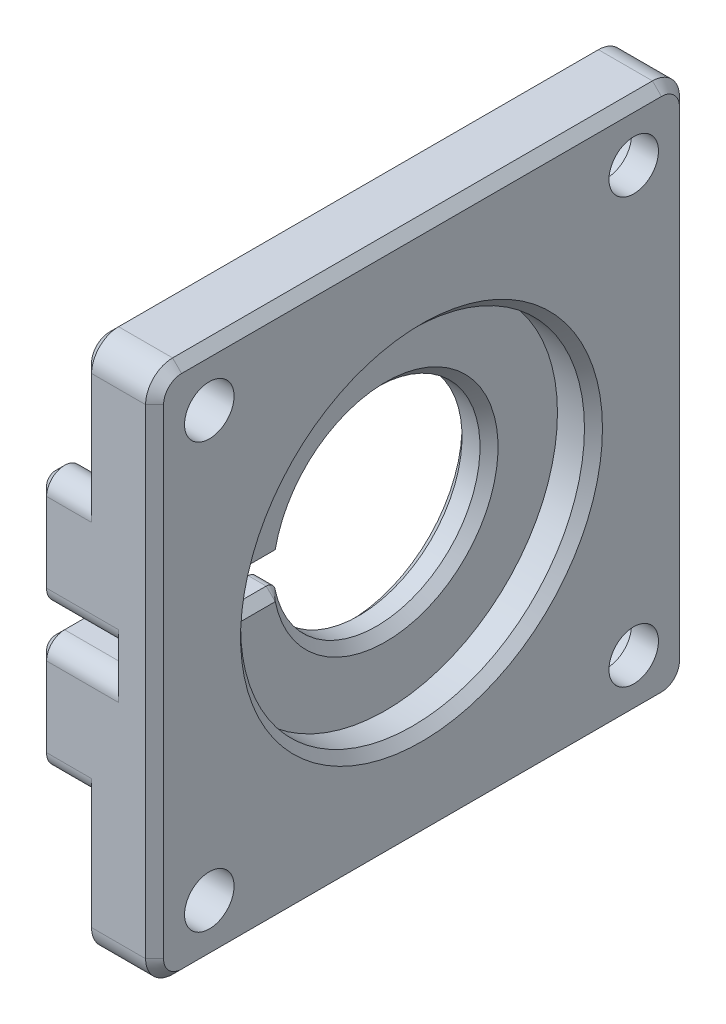
SolidWorks part; units mm, degrees
note: The reader was unsure of these and kept them because the rebuilt part matched: shared geometry of "Sketch1<3>".
ref_plane "Front Plane" through (0, 0, 0) normal (0, 0, 1) x (1, 0, 0)
ref_plane "Top Plane" through (0, 0, 0) normal (0, 1, 0) x (1, 0, 0)
ref_plane "Right Plane" through (0, 0, 0) normal (1, 0, 0) x (0, 0, -1)
sketch "Sketch1" plane through (0, 0, 0) normal (1, 0, 0) x (0, 0, -1)
  line L1 (-23.5714, 23.5714) -> (23.5714, 23.5714) construction
  line L2 (-23.5714, 23.5714) -> (-23.5714, -23.5714) construction
  line L3 (-23.5714, -23.5714) -> (23.5714, -23.5714) construction
  line L4 (23.5714, 23.5714) -> (23.5714, -23.5714) construction
  line L5 (-23.5714, 23.5714) -> (23.5714, -23.5714) construction
  line L6 (-23.5714, -23.5714) -> (23.5714, 23.5714) construction
  line L7 (-29.65, 29.65) -> (29.65, 29.65)
  line L8 (-29.65, 29.65) -> (-29.65, -29.65)
  line L9 (-29.65, -29.65) -> (29.65, -29.65)
  line L10 (29.65, 29.65) -> (29.65, -29.65)
  line L11 (-29.65, 29.65) -> (29.65, -29.65) construction
  line L12 (-29.65, -29.65) -> (29.65, 29.65) construction
  circle A0 centre (0, 0) radius 33.335 construction
  circle A1 centre (0, 0) radius 19.1
  circle A2 centre (0, 0) radius 11.5
  circle A3 centre (-23.5714, 23.5714) radius 2.75
  circle A4 centre (23.5714, 23.5714) radius 2.75
  circle A5 centre (23.5714, -23.5714) radius 2.75
  circle A6 centre (-23.5714, -23.5714) radius 2.75
  point P6 (0, 0)
  point P13 (0, 0)
  dimension "D1" = 66.67
  dimension "D3" = 38.2
  dimension "D4" = 23
  dimension "D5" = 5.5
  dimension "D2" = 59.3
extrude "Boss-Extrude1" add sketch "Sketch1" along normal blind 4 contours L10 L7 L8 L9 A1 | A3 | A4 | A5 | A6
extrude "Boss-Extrude2" add sketch "Sketch1<3>" against normal blind 4 contours L10 L7 L8 L9 A1 | A1 A2 | A4 | A3 | A6 | A5
sketch "Sketch1<3>" plane through (0, 0, 0) normal (1, 0, 0) x (0, 0, -1) same geometry as "Sketch1"
sketch "Sketch18" plane through (-4, 0, 0) normal (-1, 0, 0) x (0, 0, 1)
  line L0 (29.65, 17.15) -> (12.5, 0)
  line L1 (29.65, 29.65) -> (29.65, -29.65) construction
  line L2 (12.5, 0) -> (29.65, -17.15)
  line L3 (29.65, -17.15) -> (29.65, 17.15)
  line L4 (12.5, 0) -> (0, 0) construction
  line L5 (14, 1.5) -> (29.65, 1.5)
  line L6 (29.65, -1.5) -> (14, -1.5)
  line M7 (29.65, -29.65) -> (29.65, 29.65)
  dimension "D1" = 12.5
  dimension "D2" = 45
  dimension "D3" = 3
extrude "Boss-Extrude4" add sketch "Sketch18" along normal blind 5 contours L6 L2 M7 | L0 L5 L3
sketch "Sketch20" plane through (0, 0, 0) normal (0, 0, 1) x (1, 0, 0)
  line L0 (-4, 1.5) -> (-1.5, 1.5)
  line L1 (-1.5, -1.5) -> (-4, -1.5)
  line L2 (-4, -1.5) -> (-4, 1.5)
  line L3 (-1.5, 1.5) -> (0, 1.5)
  line L4 (0, 1.5) -> (0, -1.5)
  line L5 (0, -1.5) -> (-1.5, -1.5)
  arc A0 (-1.5, 1.5) -> (-1.5, -1.5) centre (-1.5, 0) cw
  dimension "D1" = 4
extrude "Cut-Extrude1" cut sketch "Sketch20" along normal through all contours L3 A0 L4 | A0 L0 L2 L1 | L4 A0 L5
sketch "Sketch13" plane through (-4, 0, 0) normal (1, 0, 0) x (0, 0, -1)
  point P0 (-23.5714, 23.5714)
  point P9 (-23.5714, -23.5714)
hole_wizard "M5 Clearance Hole1" positions "Sketch13" profile "Sketch12" hole size "M5" standard "ANSI Metric" end condition through all
sketch "Sketch12" plane through (-4, 23.5714, 23.5714) normal (0, 1, 0) x (0, 0, 1)
  line L0 (0, 0) -> (0, 8)
  line L1 (0, 8) -> (2.75, 8)
  line L2 (2.75, 8) -> (2.75, 0.025)
  line L3 (2.75, 0.025) -> (2.775, 0)
  line L5 (2.775, 0) -> (0, 0)
  line L6 (-2.75, 0.025) -> (-2.775, 0) construction
  line L11 (0, -6.35) -> (0, 107.95) construction
  dimension "Thru Hole Dia." = 5.5
  dimension "Thru Hole Depth" = 8
  dimension "Near C'Sink Dia." = 5.55
  dimension "Near C'Sink Angle" = 90
sketch "Sketch17" plane through (-4, 0, 0) normal (-1, 0, 0) x (0, 0, 1)
  point P0 (-23.5714, 23.5714)
  point P3 (-23.5714, -23.5714)
hole_wizard "CBORE for M5 SHCS2" positions "Sketch17" profile "Sketch16" counterbore size "M5" standard "ANSI Metric" end condition through all
sketch "Sketch16" plane through (-4, 23.5714, -23.5714) normal (0, 1, 0) x (0, 0, 1)
  line L0 (0, 0) -> (0, 8)
  line L1 (0, 8) -> (2.75, 8)
  line L3 (2.75, 8) -> (2.75, 5)
  line L4 (5, 5) -> (2.75, 5)
  line L5 (5, 5) -> (5, 0.025)
  line L6 (5, 0.025) -> (5.025, 0)
  line L7 (5.025, 0) -> (0, 0)
  line L8 (-5, 0.025) -> (-5.025, 0) construction
  line L11 (0, -6.35) -> (0, 107.95) construction
  dimension "Thru Hole Dia." = 5.5
  dimension "Thru Hole Depth" = 8
  dimension "C'Bore Dia." = 10
  dimension "C'Bore Depth" = 5
  dimension "Near C'Sink Dia." = 10.05
  dimension "Near C'Sink Angle" = 90
sketch "Sketch4" [suppressed] plane through (0, 0, 0) normal (1, 0, 0) x (0, 0, -1)
  line L0 (8, -29.65) -> (8, -59.65)
  line L1 (-29.65, -29.65) -> (29.65, -29.65) construction
  line L2 (8, -59.65) -> (0, -59.65)
  line L3 (0, -59.65) -> (0, -39.65)
  line L4 (0, -39.65) -> (-25, -39.65)
  line L5 (-25, -39.65) -> (-25, -29.65)
  line L6 (-25, -29.65) -> (8, -29.65)
  dimension "D1" = 10
  dimension "D2" = 8
  dimension "D3" = 25
  dimension "D4" = 30
fillet "Fillet6" radius 3 4 edges at (0, 29.65, 29.65) (0, 29.65, -29.65) (0, -29.65, 29.65) (0, -29.65, -29.65)
fillet "Fillet4" radius 2 6 edges at (-6.5, -17.15, 29.65) (-6.5, 17.15, 29.65) (-6.5, -1.5, 14) (-6.5, 1.5, 14) (-4.5, -1.5, 29.65) (-4.5, 1.5, 29.65)
fillet "Fillet5" radius 1 2 edges at (-2, -1.5, 11.4018) (-2, 1.5, 11.4018)
chamfer "Chamfer1" distance 1 angle 45 40 edges at (4, 0, -19.1) (-4, -1.5, 15.5379) (-4, 1.5, 15.5379) (-4, -1.7254, 11.615) (0, -1.7254, 11.615) (0, 1.7254, 11.615) (-4, 1.7254, 11.615) (-4, 0, -11.5) (0, 0, -11.5) (0, -1.5, 15.6442) (0, 1.5, 15.6442) (4, -29.65, 0) (4, -28.7713, 28.7713) (4, -28.7713, -28.7713) (4, 0, 29.65) (4, 0, -29.65) (4, 28.7713, 28.7713) (4, 28.7713, -28.7713) (4, 29.65, 0) (-9, -2.0858, 29.0642) (-9, -1.5, 23.2392) (-9, -7.9108, 29.65) (-9, -2.7346, 16.9807) (-9, -14.1693, 28.4154) (-9, -9.325, 21.825) (-9, 2.0858, 29.0642) (-9, 7.9108, 29.65) (-9, 1.5, 23.2392) (-9, 14.1693, 28.4154) (-9, 2.7346, 16.9807) (-9, 9.325, 21.825) (-4, -19.4858, 29.65) (-4, -28.7713, 28.7713) (-4, -29.65, 0) (-4, -28.7713, -28.7713) (-4, 19.4858, 29.65) (-4, 0, -29.65) (-4, 28.7713, 28.7713) (-4, 28.7713, -28.7713) (-4, 29.65, 0)
